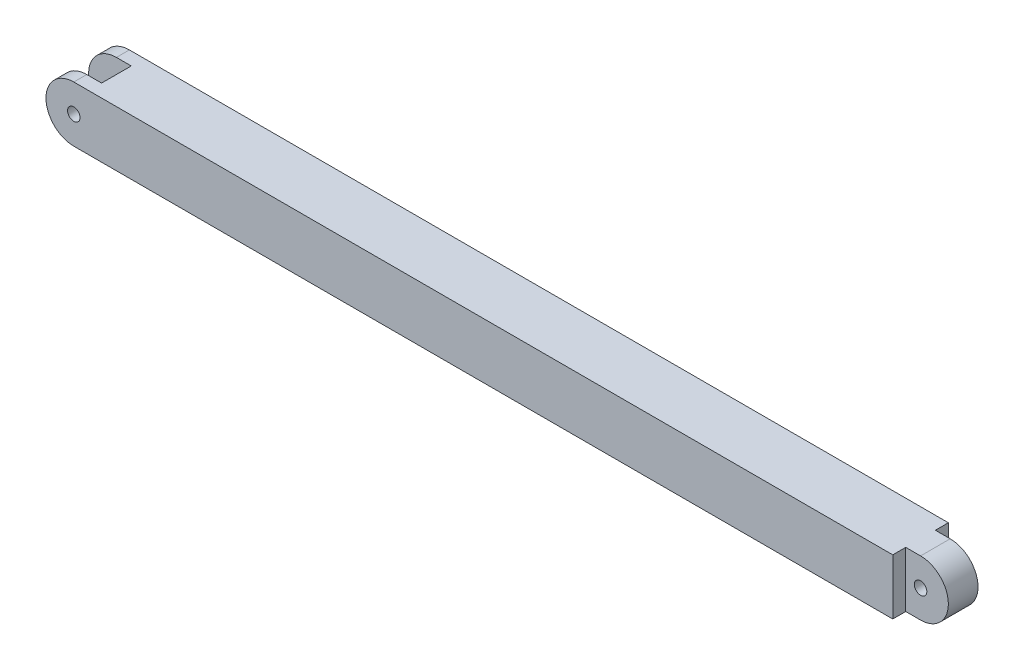
SolidWorks part; units mm, degrees
ref_plane "Front Plane" through (0, 0, 0) normal (0, 0, 1) x (1, 0, 0)
ref_plane "Top Plane" through (0, 0, 0) normal (0, 1, 0) x (1, 0, 0)
ref_plane "Right Plane" through (0, 0, 0) normal (1, 0, 0) x (0, 0, -1)
sketch "Sketch1" plane through (0, 0, 0) normal (0, 0, 1) x (1, 0, 0)
  line L0 (-225, 0) -> (225, 0) construction
  line L1 (-225, 15) -> (225, 15)
  line L2 (-225, -15) -> (225, -15)
  arc A0 (-225, 15) -> (-225, -15) centre (-225, 0) ccw
  arc A1 (225, -15) -> (225, 15) centre (225, 0) ccw
  point P2 (0, 0)
  dimension "D1" = 450
  dimension "D2" = 30
extrude "Boss-Extrude1" add sketch "Sketch1" along normal mid plane 30
hole_wizard "H (0.266) Diameter Hole1" positions "Sketch2" profile "Sketch4" hole size "H" standard "ANSI Inch" end condition through all
sketch "Sketch2" plane through (0, 0, 15) normal (0, 0, 1) x (1, 0, 0)
  point P0 (-225, 0)
  point P3 (225, 0)
sketch "Sketch4" plane through (-225, 0, 15) normal (1, 0, 0) x (0, -1, 0)
  line L0 (0, 0) -> (0, 30)
  line L1 (0, 30) -> (3.3782, 30)
  line L2 (3.3782, 30) -> (3.3782, 0)
  line L5 (3.3782, 0) -> (0, 0)
  line L11 (0, -6.35) -> (0, 107.95) construction
  dimension "Thru Hole Dia." = 6.7564
  dimension "Thru Hole Depth" = 30
sketch "Sketch5" plane through (0, 15, 0) normal (0, 1, 0) x (1, 0, 0)
  line L1 (-257, 8) -> (-217, 8)
  line L2 (-257, 8) -> (-257, -8)
  line L3 (-257, -8) -> (-217, -8)
  line L4 (-217, 8) -> (-217, -8)
  line L5 (-217, 0) -> (0, 0) construction
  line L6 (-225, -15) -> (-225, 15) construction
  line L7 (225, -15) -> (225, 15) construction
  line L8 (217, 28.9161) -> (257, 28.9161)
  line L9 (217, 28.9161) -> (217, 8)
  line L10 (217, 8) -> (257, 8)
  line L11 (257, 28.9161) -> (257, 8)
  line L12 (217, -28.9161) -> (257, -28.9161)
  line L13 (217, -28.9161) -> (217, -8)
  line L14 (217, -8) -> (257, -8)
  line L15 (257, -28.9161) -> (257, -8)
  dimension "D1" = 16
  dimension "D2" = 8
  dimension "D3" = 40
  dimension "D4" = 8
extrude "Cut-Extrude1" cut sketch "Sketch5" against normal through all
